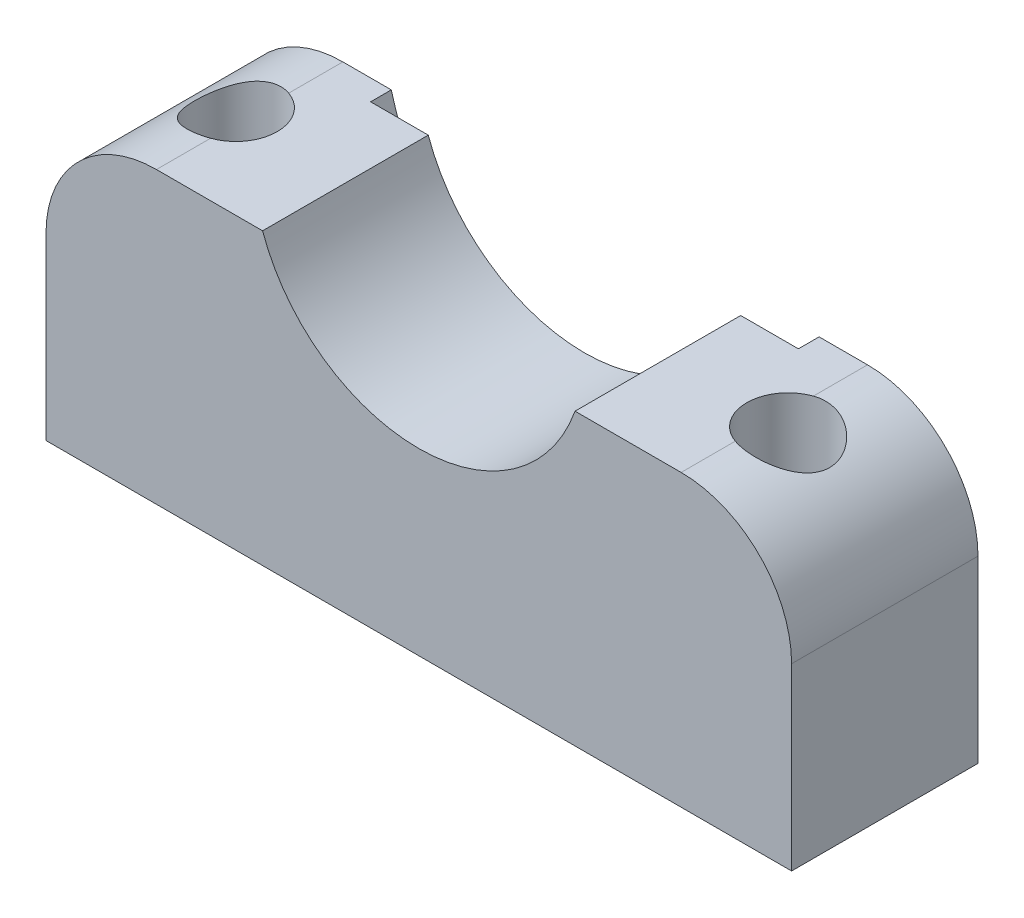
SolidWorks part; units mm, degrees
ref_plane "Front Plane" through (0, 0, 0) normal (0, 0, 1) x (1, 0, 0)
ref_plane "Top Plane" through (0, 0, 0) normal (0, 1, 0) x (1, 0, 0)
ref_plane "Right Plane" through (0, 0, 0) normal (1, 0, 0) x (0, 0, -1)
sketch "Sketch1" plane through (0, 0, 0) normal (0, 0, 1) x (1, 0, 0)
  line L1 (0, 0) -> (-27, 0)
  line L2 (0, 0) -> (0, 12.5)
  line L3 (0, 12.5) -> (-27, 12.5)
  line L4 (-27, 0) -> (-27, 12.5)
  circle A0 centre (-13.5, 12.5) radius 6
  dimension "D3" = 12
  dimension "D1" = 27
  dimension "D2" = 12.5
extrude "Boss-Extrude1" add sketch "Sketch1" along normal blind 6.75 contours A0 L3 L4 L1 L2 region at (-13.5, 5.5046, 0)
sketch "Sketch3" plane through (0, 0, 0) normal (0, 0, -1) x (-1, 0, 0)
  circle A0 centre (13.5, 12.5) radius 8
  dimension "D1" = 16
extrude "Cut-Extrude2" cut sketch "Sketch3" against normal blind 0.75
sketch "Sketch4" plane through (0, 0, 6.75) normal (0, 0, 1) x (1, 0, 0)
  line L0 (-27, 0) -> (-27, 12.5) construction
  line L1 (0, 12.5) -> (-27, 12.5)
  line L2 (0, 12.5) -> (0, 10.5)
  line L3 (0, 10.5) -> (-27, 10.5)
  line L4 (-27, 12.5) -> (-27, 10.5)
  line L5 (0, 0) -> (0, 12.5) construction
  line L6 (0, 12.5) -> (-7.5, 12.5) construction
  dimension "D1" = 2
extrude "Cut-Extrude3" cut sketch "Sketch4" against normal blind 9
sketch "Sketch5" plane through (0, 0, 0) normal (0, -1, 0) x (1, 0, 0)
  line L0 (-27, 3.375) -> (0, 3.375) construction
  line L1 (-27, 6.75) -> (-27, 0) construction
  line L2 (0, 6.75) -> (0, 0) construction
  circle A0 centre (-23.5, 3.375) radius 1.5
  circle A1 centre (-3.5, 3.375) radius 1.5
  dimension "D1" = 3
  dimension "D2" = 3.5
  dimension "D3" = 3.5
extrude "Cut-Extrude4" cut sketch "Sketch5" against normal blind 16
fillet "Fillet1" radius 4 2 edges at (-27, 10.5, 3.375) (0, 10.5, 3.375)
